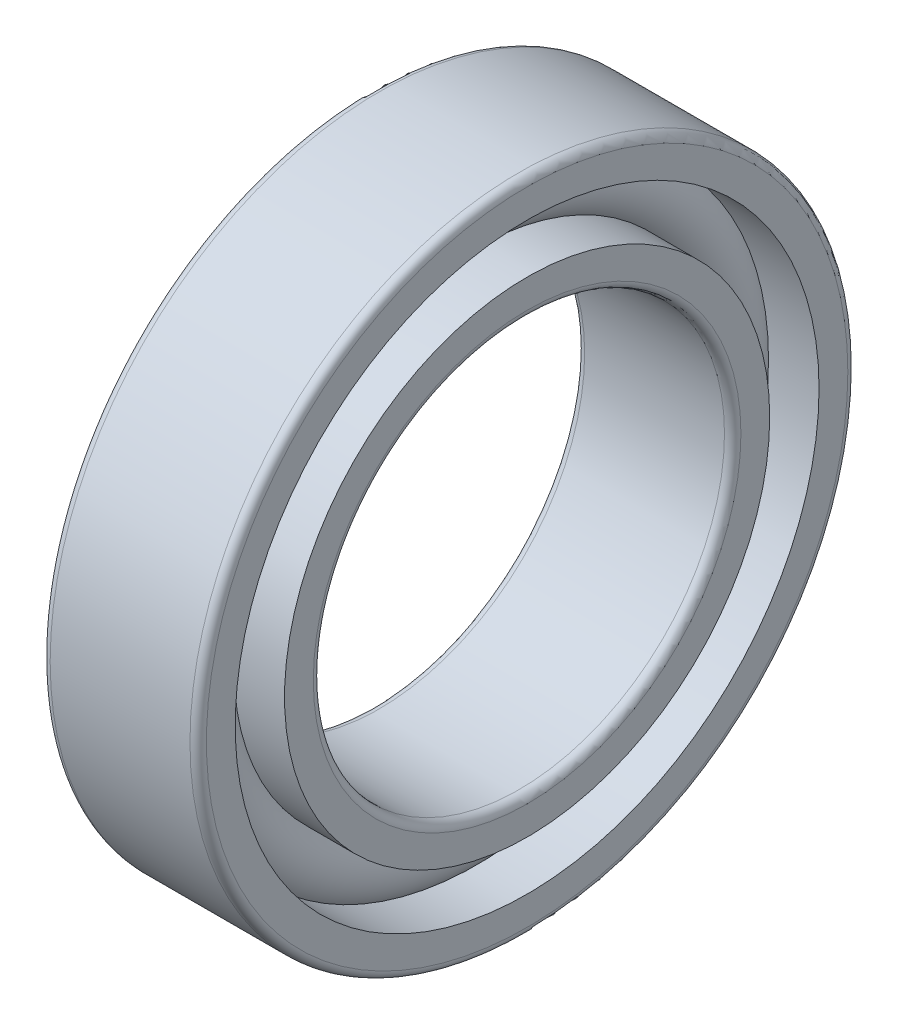
SolidWorks part; units mm, degrees
material "Stainless Steel (ferritic)"
ref_plane "Plane1" through (0, 0, 0) normal (0, 0, 1) x (1, 0, 0)
ref_plane "Plane2" through (0, 0, 0) normal (0, 1, 0) x (1, 0, 0)
ref_plane "Plane3" through (0, 0, 0) normal (1, 0, 0) x (0, 0, -1)
sketch "Clipboard" plane through (0, 0, 0) normal (0, 0, 1) x (1, 0, 0)
  line L0 (-10, 0) -> (10, 0) construction
  line L1 (0, 0) -> (22.3471, -0.7804)
  line L2 (0, 0) -> (32.4802, 1.1342)
  line L3 (0, 0) -> (22.3471, -0.7804)
  line L4 (0, 0) -> (-22.3573, -0.3902)
  dimension "BallCLRad" = 32.5
sketch "CagSpiSke" plane through (0, 0, 0) normal (0, 0, 1) x (1, 0, 0)
  line L0 (0.45, 31.75) -> (0.45, 33.25)
  line L1 (0.45, 33.25) -> (-0.45, 33.25)
  line L2 (-0.45, 33.25) -> (-0.45, 31.75)
  line L3 (-0.45, 31.75) -> (0.45, 31.75)
  line L4 (-20.6375, 0) -> (20.6375, 0) construction
  line L5 (0, 0) -> (0, 23.7692) construction
  dimension "OD" = 66.5
  dimension "ID" = 63.5
revolve "CageSpine" add sketch "CagSpiSke" angle 0.001 about L4 reverse direction yes
ref_axis "Axis1" through (-50, 0, 0) along (1, 0, 0)
sketch "CagBalSke" plane through (0, 0, 0) normal (0, 0, 1) x (1, 0, 0)
  line L0 (-4.95, 32.5) -> (4.95, 32.5)
  line L1 (-1.905, 32.5) -> (1.905, 32.5) construction
  line L2 (-10, 0) -> (10, 0) construction
  line L3 (0, 0) -> (0, 24) construction
  arc A0 (4.95, 32.5) -> (-4.95, 32.5) centre (0, 32.5) cw
  dimension "BallCLRad" = 32.5
revolve "CageBall" [suppressed] add sketch "CagBalSke" angle 360 about L1 reverse direction yes
pattern_circular "CageBalls" [suppressed] count 2 every 180 about axis through (-50, 0, 0) along (1, 0, 0)
sketch "CagTrmODSke" plane through (0, 0, 0) normal (0, 0, 1) x (1, 0, 0)
  line L0 (4.951, 33.25) -> (4.951, 37.451)
  line L1 (4.951, 37.451) -> (-4.951, 37.451)
  line L2 (-4.951, 37.451) -> (-4.951, 33.25)
  line L3 (-4.951, 33.25) -> (4.951, 33.25)
  line L4 (-20.6375, 0) -> (20.6375, 0) construction
  line L5 (0, 0) -> (0, 25) construction
  dimension "Width" = 9.902
  dimension "ID" = 66.5
  dimension "OD" = 74.902
revolve "CageTrimOD" [suppressed] cut sketch "CagTrmODSke" angle 360 about L4 reverse direction yes
sketch "CagTrmIDSke" plane through (0, 0, 0) normal (0, 0, 1) x (1, 0, 0)
  line L0 (4.951, 27.551) -> (4.951, 31.75)
  line L1 (4.951, 31.75) -> (-4.951, 31.75)
  line L2 (-4.951, 31.75) -> (-4.951, 27.551)
  line L3 (-4.951, 27.551) -> (4.951, 27.551)
  line L4 (-20.6375, 0) -> (20.6375, 0) construction
  line L5 (0, 0) -> (0, 25) construction
  dimension "Width" = 9.902
  dimension "ID" = 55.102
  dimension "OD" = 63.5
revolve "CageTrimID" [suppressed] cut sketch "CagTrmIDSke" angle 360 about L4 reverse direction yes
sketch "BalSimSke" plane through (0, 0, 0) normal (0, 0, 1) x (1, 0, 0)
  line L0 (-10, 0) -> (10, 0) construction
  line L1 (-10, 32.5) -> (10, 32.5) construction
  line L2 (0, 0) -> (0, 23) construction
  circle A0 centre (0, 32.5) radius 4.5
  dimension "BallCLRad" = 32.5
  dimension "Ball_diameter" = 9
revolve "BallsSimplified" add sketch "BalSimSke" angle 360 about L0
sketch "BalDetSke" plane through (0, 0, 0) normal (0, 0, 1) x (1, 0, 0)
  line L0 (-4.5, 32.5) -> (4.5, 32.5)
  line L1 (-1.905, 32.5) -> (1.905, 32.5) construction
  line L2 (0, 0) -> (0, 25) construction
  arc A0 (4.5, 32.5) -> (-4.5, 32.5) centre (0, 32.5) cw
  dimension "BallCLRad" = 32.5
  dimension "Ball_diameter" = 9
revolve "BallDetailed" [suppressed] add sketch "BalDetSke" angle 360 about L1 reverse direction yes
sketch "InnRacSke" plane through (0, 0, 0) normal (0, 0, 1) x (1, 0, 0)
  line L0 (-3.3205, 29.5) -> (-9.5, 29.5)
  line L1 (-9.5, 29.5) -> (-9.5, 26)
  line L2 (-8.5, 25) -> (8.5, 25)
  line L3 (9.5, 26) -> (9.5, 29.5)
  line L4 (9.5, 29.5) -> (3.3205, 29.5)
  line L5 (-20.6375, 0) -> (20.6375, 0) construction
  line L6 (0, 0) -> (0, 30) construction
  arc A0 (-9.5, 26) -> (-8.5, 25) centre (-8.5, 26) ccw
  arc A1 (8.5, 25) -> (9.5, 26) centre (8.5, 26) ccw
  arc A2 (3.3205, 29.5) -> (-3.3205, 29.5) centre (0, 32.5) cw
  dimension "BallCLRad" = 32.5
  dimension "Fillet_radius" = 1
  dimension "Ball_diameter" = 8.95
  dimension "ID" = 50
  dimension "OD" = 59
  dimension "Width" = 19
revolve "InnerRace" add sketch "InnRacSke" angle 360 about L5 reverse direction yes
sketch "OutRacSke" plane through (0, 0, 0) normal (0, 0, 1) x (1, 0, 0)
  line L0 (-3.3205, 35.5) -> (-9.5, 35.5)
  line L1 (-9.5, 35.5) -> (-9.5, 39)
  line L2 (-8.5, 40) -> (8.5, 40)
  line L3 (9.5, 39) -> (9.5, 35.5)
  line L4 (9.5, 35.5) -> (3.3205, 35.5)
  line L5 (-20.6375, 0) -> (20.6375, 0) construction
  line L6 (0, 0) -> (0, 30) construction
  arc A0 (-9.5, 39) -> (-8.5, 40) centre (-8.5, 39) cw
  arc A1 (8.5, 40) -> (9.5, 39) centre (8.5, 39) cw
  arc A2 (3.3205, 35.5) -> (-3.3205, 35.5) centre (0, 32.5) ccw
  dimension "BallCLRad" = 32.5
  dimension "Fillet_radius" = 1
  dimension "Ball_diameter" = 8.95
  dimension "Width" = 19
revolve "OuterRace" add sketch "OutRacSke" angle 360 about L5 reverse direction yes
pattern_circular "BallsDetailed" [suppressed] count 2 every 180 about axis through (-50, 0, 0) along (1, 0, 0)
equation "\"BallCLRad@Clipboard\" = ( \"OD@OutRacSke\" + \"ID@InnRacSke\" ) / 4"
equation "\"BallCLRad@BalSimSke\" = \"BallCLRad@Clipboard\""
equation "\"BallCLRad@BalDetSke\" = \"BallCLRad@Clipboard\""
equation "\"BallCLRad@InnRacSke\" = \"BallCLRad@Clipboard\""
equation "\"BallCLRad@OutRacSke\" = \"BallCLRad@Clipboard\""
equation "\"Ball_diameter@InnRacSke\" = \"Ball_diameter@BalDetSke\" - 0.05"
equation "\"Ball_diameter@OutRacSke\" = \"Ball_diameter@BalDetSke\" - 0.05"
equation "\"Ball_diameter@BalSimSke\" = \"Ball_diameter@BalDetSke\""
equation "\"Width@OutRacSke\" = \"Width@InnRacSke\""
equation "\"Fillet_radius@OutRacSke\" = \"Fillet_radius@InnRacSke\""
equation "\"Max_count@Clipboard\" = int( 3.14159265 / atn(( \"Ball_diameter@BalDetSke\" / 2) / sqr( \"BallCLRad@Clipboard\"  *  \"BallCLRad@Clipboard\" - ( \"Ball_diameter@BalDetSke\" / 2) *  ( \"Ball_diameter@BalDetSke\" / 2))))"
equation "\"Max_count@Clipboard\" = ((sgn( \"Max_count@Clipboard\" - \"Count@Clipboard\" )-1)*( \"Max_count@Clipboard\" - \"Count@Clipboard\" ))/-2+ \"Count@Clipboard\""
equation "\"Count@BallsDetailed\" = int( \"Show_count@Clipboard\" ) "
equation "\"Count@BallsDetailed\" = ((sgn( \"Count@BallsDetailed\" - \"Max_count@Clipboard\" )-1)*( \"Count@BallsDetailed\" - \"Max_count@Clipboard\" ))/-2+ \"Max_count@Clipboard\""
equation "\"Count@BallsDetailed\" = ((sgn( \"Count@BallsDetailed\" - \"Min_count@Clipboard\" )+1)*( \"Count@BallsDetailed\" - \"Min_count@Clipboard\"))/2 +\"Min_count@Clipboard\""
equation "\"Angle@BallsDetailed\" = 360.0 / \"Max_count@Clipboard\""
equation "\"BallCLRad@CagBalSke\" = \"BallCLRad@Clipboard\""
equation "\"Count@CageBalls\" = \"Count@BallsDetailed\""
equation "\"Angle@CageBalls\" = \"Angle@BallsDetailed\""
equation "\"Angle@CageSpine\" =  \"Angle@CageBalls\" * ( \"Count@CageBalls\" -1 + int( \"Count@CageBalls\" / \"Max_count@Clipboard\" ) )  + 0.001 -  int( \"Count@CageBalls\" / \"Max_count@Clipboard\" ) * 0.001"
equation "\"Angle@CageSpine\" =  \"Angle@CageSpine\" * int( \"Min_count@Clipboard\" / 2) + int(1 / \"Min_count@Clipboard\")  * 0.001"
equation "\"CageWallOD@CagBalSke\" =  \"Ball_diameter@BalDetSke\" * 1.1"
equation "\"Thickness@CagSpiSke\" =  \"Ball_diameter@BalDetSke\" * 0.1"
equation "\"OD@CagTrmODSke\" = \"BallCLRad@Clipboard\" * 2 + \"CageWallOD@CagBalSke\" + 0.002"
equation "\"ID@CagTrmODSke\" = \"BallCLRad@Clipboard\" * 2 + \"Ball_diameter@BalDetSke\" / 6"
equation "\"OD@CagTrmIDSke\" = \"BallCLRad@Clipboard\" * 2 - \"Ball_diameter@BalDetSke\" / 6"
equation "\"ID@CagTrmIDSke\" = \"BallCLRad@Clipboard\" * 2 - \"CageWallOD@CagBalSke\" + 0.002"
equation "\"OD@CagSpiSke\" = \"ID@CagTrmODSke\""
equation "\"ID@CagSpiSke\" = \"OD@CagTrmIDSke\""
equation "\"Width@CagTrmODSke\" = \"CageWallOD@CagBalSke\" + 0.002"
equation "\"Width@CagTrmIDSke\" = \"CageWallOD@CagBalSke\" + 0.002"
